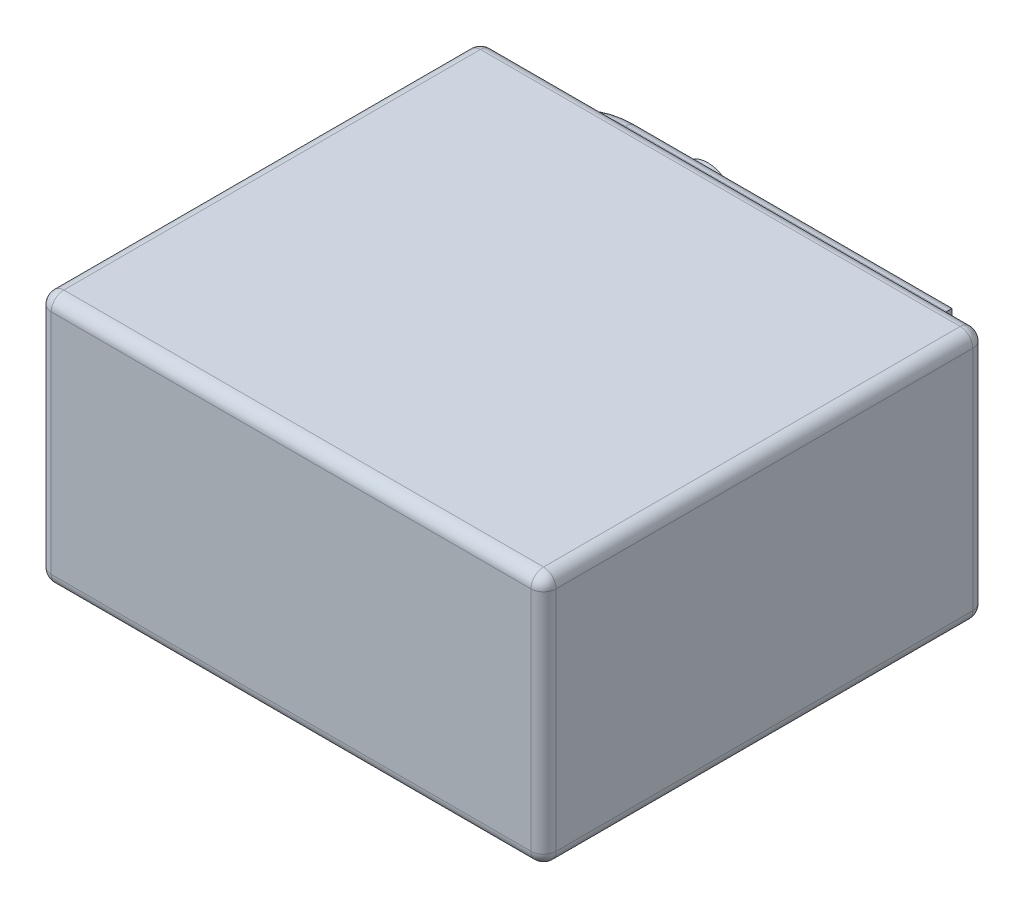
SolidWorks part; units mm, degrees
ref_plane "前视基准面" through (0, 0, 0) normal (0, 0, 1) x (1, 0, 0)
ref_plane "上视基准面" through (0, 0, 0) normal (0, 1, 0) x (1, 0, 0)
ref_plane "右视基准面" through (0, 0, 0) normal (1, 0, 0) x (0, 0, -1)
sketch "草图1" plane through (0, 0, 0) normal (0, 0, 1) x (1, 0, 0)
  line L1 (-20, 10) -> (20, 10)
  line L2 (-20, 10) -> (-20, -10)
  line L3 (-20, -10) -> (20, -10)
  line L4 (20, 10) -> (20, -10)
  line L5 (-20, 10) -> (20, -10) construction
  line L6 (-20, -10) -> (20, 10) construction
  point P0 (0, 0)
  dimension "D1" = 20
  dimension "D2" = 40
extrude "凸台-拉伸1" add sketch "草图1" along normal blind 35
fillet "圆角1" radius 1 12 edges at (-20, 0, 35) (20, 0, 35) (20, 10, 17.5) (0, 10, 35) (-20, 10, 17.5) (0, 10, 0) (-20, 0, 0) (20, 0, 0) (-20, -10, 17.5) (0, -10, 35) (20, -10, 17.5) (0, -10, 0)
sketch "草图2" plane through (0, 0, 0) normal (0, 0, -1) x (-1, 0, 0)
  line L0 (20, 9) -> (20, -9) construction
  circle A0 centre (10, 0) radius 2.2404
  dimension "D1" = 10
extrude "凸台-拉伸2" add sketch "草图2" along normal blind 8
sketch "草图3" plane through (0, 0, 0) normal (0, 0, -1) x (-1, 0, 0)
  line L0 (-15.4441, 8) -> (-15.4441, -8)
  line L1 (10, 8) -> (-15.4441, 8)
  line L2 (10, -8) -> (-15.4441, -8)
  arc A0 (10, -8) -> (10, 8) centre (10, 0) ccw
  dimension "D1" = 16
extrude "凸台-拉伸3" add sketch "草图3" along normal blind 2.5
fillet "圆角2" radius 1 9 edges at (15.4441, 0, 0) (2.722, 8, -2.5) (-18, 0, -2.5) (2.722, 8, 0) (-18, 0, 0) (15.4441, -8, -1.25) (2.722, -8, -2.5) (2.722, -8, 0) (15.4441, 0, -2.5)
